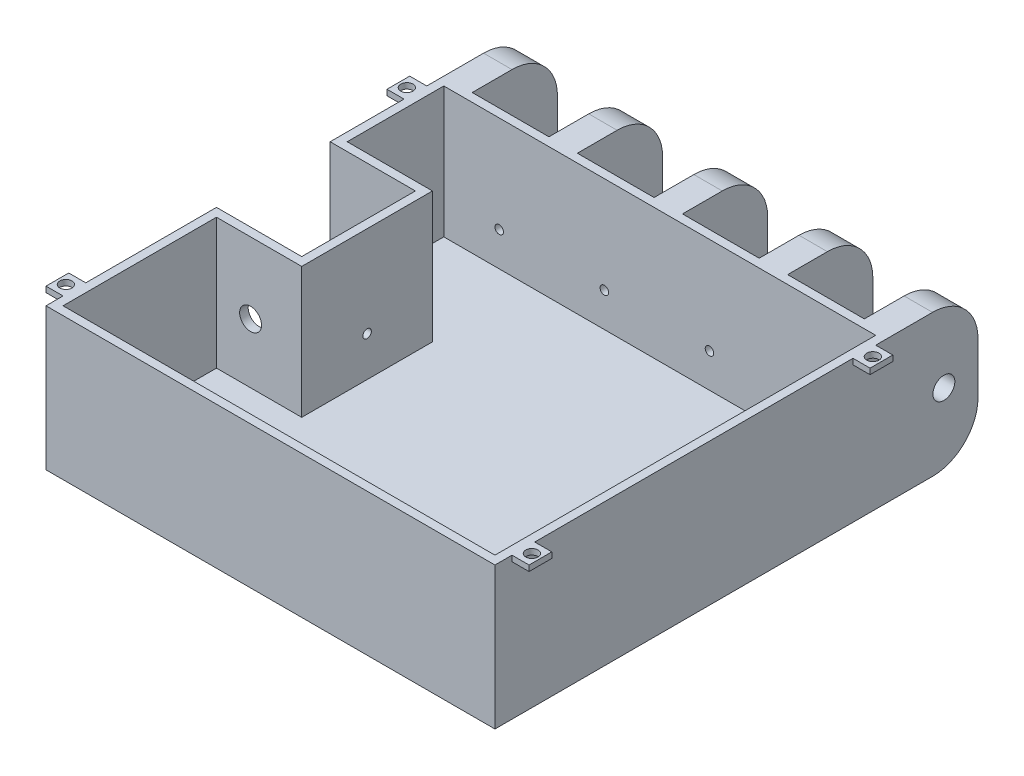
SolidWorks part; units mm, degrees
ref_plane "Front Plane" through (0, 0, 0) normal (0, 0, 1) x (1, 0, 0)
ref_plane "Top Plane" through (0, 0, 0) normal (0, 1, 0) x (1, 0, 0)
ref_plane "Right Plane" through (0, 0, 0) normal (1, 0, 0) x (0, 0, -1)
sketch "Sketch2" plane through (0, 0, 0) normal (0, 1, 0) x (1, 0, 0)
  line L0 (0, 0) -> (79, 0)
  line L1 (79, 0) -> (79, 85)
  line L2 (79, 85) -> (74, 85)
  line L3 (74, 85) -> (74, 70)
  line L4 (74, 70) -> (60.5, 70)
  line L5 (60.5, 70) -> (60.5, 85)
  line L6 (60.5, 85) -> (55.5, 85)
  line L7 (55.5, 85) -> (55.5, 70)
  line L8 (55.5, 70) -> (42, 70)
  line L9 (42, 70) -> (42, 85)
  line L10 (42, 85) -> (37, 85)
  line L11 (37, 85) -> (37, 70)
  line L12 (37, 70) -> (23.5, 70)
  line L13 (23.5, 70) -> (23.5, 85)
  line L14 (23.5, 85) -> (18.5, 85)
  line L15 (18.5, 85) -> (18.5, 70)
  line L16 (18.5, 70) -> (5, 70)
  line L17 (5, 70) -> (5, 85)
  line L18 (5, 85) -> (0, 85)
  line L19 (0, 85) -> (0, 50)
  line L20 (0, 50) -> (15, 50)
  line L21 (15, 50) -> (15, 30)
  line L22 (15, 30) -> (0, 30)
  line L23 (0, 30) -> (0, 0)
  dimension "D1" = 5
  dimension "D2" = 5
  dimension "D3" = 5
  dimension "D4" = 79
  dimension "D5" = 5
  dimension "D6" = 5
  dimension "D7" = 13.5
  dimension "D8" = 13.5
  dimension "D9" = 13.5
  dimension "D10" = 85
  dimension "D11" = 85
  dimension "D12" = 15
  dimension "D13" = 15
  dimension "D14" = 15
  dimension "D15" = 15
  dimension "D16" = 15
  dimension "D17" = 15
  dimension "D18" = 15
  dimension "D19" = 20
  dimension "D20" = 20
  dimension "D21" = 15
extrude "Boss-Extrude1" add sketch "Sketch2" along normal blind 25
sketch "Sketch3" plane through (74, 0, 0) normal (-1, 0, 0) x (0, 0, 1)
  line L0 (-85, 25) -> (-85, 0) construction
  line L1 (-85, 0) -> (-70, 0) construction
  circle A0 centre (-79, 12.5) radius 1.925
  dimension "D3" = 3.85
  dimension "D1" = 6
  dimension "D2" = 12.5
sketch "Sketch4" plane through (0, 25, 0) normal (0, 1, 0) x (1, 0, 0)
  line L0 (0, 50) -> (15, 50)
  line L1 (15, 50) -> (15, 30)
  line L2 (15, 30) -> (0, 30)
  line L3 (0, 30) -> (0, 0)
  line L4 (0, 0) -> (79, 0)
  line L5 (79, 0) -> (79, 70)
  line L6 (79, 0) -> (79, 85) construction
  line L7 (79, 70) -> (0, 70)
  line L8 (0, 85) -> (0, 50) construction
  line L9 (0, 70) -> (0, 50)
  line L10 (1.5, 68.5) -> (1.5, 51.5)
  line L11 (1.5, 51.5) -> (16.5, 51.5)
  line L12 (16.5, 51.5) -> (16.5, 28.5)
  line L13 (16.5, 28.5) -> (1.5, 28.5)
  line L14 (1.5, 28.5) -> (1.5, 1.5)
  line L15 (1.5, 1.5) -> (77.5, 1.5)
  line L16 (77.5, 1.5) -> (77.5, 68.5)
  line L17 (77.5, 68.5) -> (1.5, 68.5)
  dimension "D1" = 70
  dimension "D2" = 1.5
extrude "Cut-Extrude2" cut sketch "Sketch4" against normal blind 23 contours L10 L11 L12 L13 L14 L15 L16 L17
sketch "Sketch9" plane through (0, 0, -50) normal (0, 0, 1) x (1, 0, 0)
  line L0 (0, 25) -> (15, 25) construction
  line L1 (0, 25) -> (0, 0) construction
  circle A0 centre (7.5, 12.5) radius 1.925
  dimension "D3" = 3.85
  dimension "D1" = 12.5
  dimension "D2" = 7.5
fillet "Fillet1" radius 8 10 edges at (2.5, 0, -85) (21, 0, -85) (39.5, 0, -85) (58, 0, -85) (76.5, 0, -85) (76.5, 25, -85) (58, 25, -85) (39.5, 25, -85) (21, 25, -85) (2.5, 25, -85)
sketch "Sketch10" plane through (0, 0, -68.5) normal (0, 0, 1) x (1, 0, 0)
  line L0 (77.5, 25) -> (1.5, 25) construction
  line L1 (1.5, 2) -> (1.5, 25) construction
  circle A0 centre (11.25, 8) radius 0.75
  dimension "D1" = 1.5
  dimension "D2" = 17
  dimension "D3" = 9.75
extrude "Cut-Extrude4" cut sketch "Sketch10" against normal blind 2 contours A0
pattern_linear "LPattern2" count 2 spacing 2 along (0, 0, -1) count 4 spacing 18.5 along (1, 0, 0) of "Cut-Extrude4"
sketch "Sketch11" plane through (16.5, 0, 0) normal (1, 0, 0) x (0, 0, -1)
  line L1 (28.5, 2) -> (28.5, 25) construction
  line L2 (51.5, 25) -> (28.5, 25) construction
  circle A0 centre (40, 9) radius 0.75
  dimension "D3" = 1.5
  dimension "D1" = 11.5
  dimension "D2" = 16
extrude "Cut-Extrude5" cut sketch "Sketch11" against normal blind 2
sketch "Sketch13" plane through (79, 0, 0) normal (1, 0, 0) x (0, 0, -1)
  line L0 (0, 25) -> (77, 25) construction
  line L1 (3, 25) -> (7, 25)
  line L2 (3, 25) -> (3, 24)
  line L3 (3, 24) -> (7, 24)
  line L4 (7, 25) -> (7, 24)
  line L5 (0, 25) -> (0, 0) construction
  dimension "D1" = 1
  dimension "D2" = 4
  dimension "D3" = 3
extrude "Boss-Extrude4" add sketch "Sketch13" along normal blind 3
sketch "Sketch14" plane through (0, 24, 0) normal (0, -1, 0) x (-1, 0, 0)
  line L0 (-82, 3) -> (-82, 7) construction
  line L1 (-82, 7) -> (-79, 7) construction
  circle A0 centre (-80.5, 5) radius 1.0783
  dimension "D1" = 1.5
  dimension "D2" = 2
extrude "Cut-Extrude6" cut sketch "Sketch14" against normal through all contours A0
pattern_linear "LPattern3" count 2 spacing 60 along (0, 0, -1) count 2 spacing 82 along (-1, 0, 0) of "Boss-Extrude4"
pattern_linear "LPattern4" count 2 spacing 60 along (0, 0, -1) count 2 spacing 82 along (-1, 0, 0) of "Cut-Extrude6"
extrude "Cut-Extrude7" cut sketch "Sketch3" along normal through all and the other way blind 19
extrude "Cut-Extrude8" cut sketch "Sketch9" along normal blind 25 and the other way blind 5
